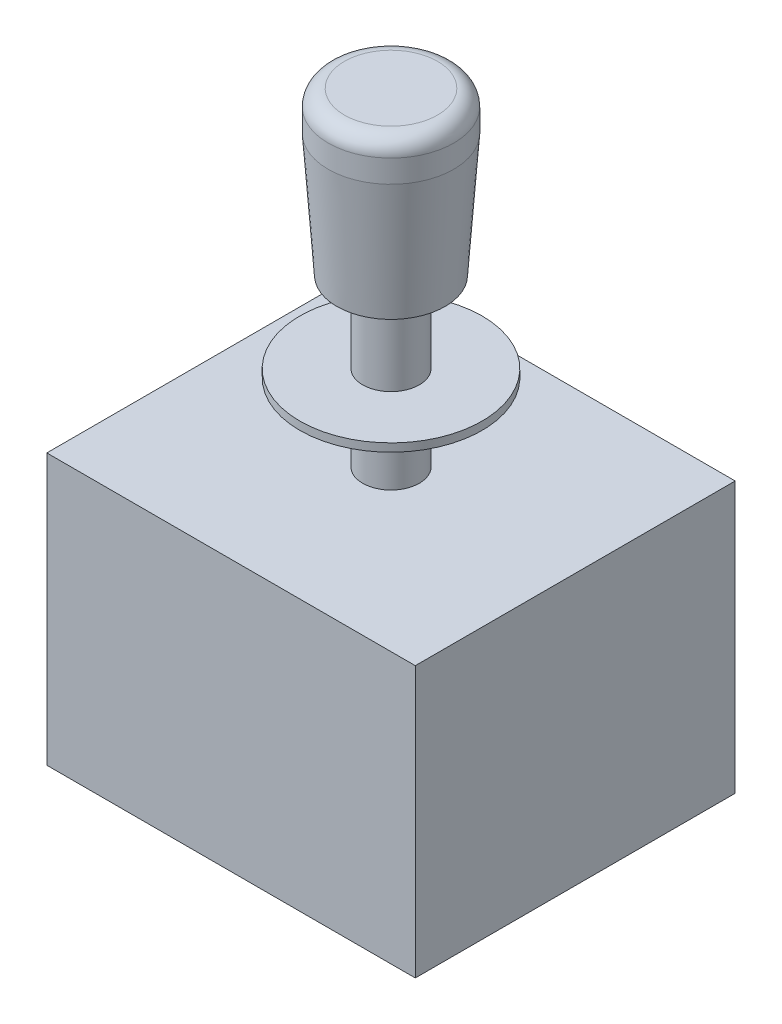
SolidWorks part; units mm, degrees
ref_plane "Front Plane" through (0, 0, 0) normal (0, 0, 1) x (1, 0, 0)
ref_plane "Top Plane" through (0, 0, 0) normal (0, 1, 0) x (1, 0, 0)
ref_plane "Right Plane" through (0, 0, 0) normal (1, 0, 0) x (0, 0, -1)
sketch "Sketch1" plane through (0, 0, 0) normal (0, 0, 1) x (1, 0, 0)
  line L0 (0, 0) -> (-7, 0)
  line L1 (-7, 0) -> (-7, 41)
  line L2 (-7, 41) -> (-13.3697, 41)
  line L3 (-13.3697, 41) -> (-15.5, 71.4018)
  line L4 (-15.5, 71.4018) -> (-15.5, 77)
  line L5 (-11.5, 81) -> (0, 81)
  line L6 (0, 81) -> (0, 0)
  line L7 (0, 0) -> (0, -10.9846) construction
  arc A0 (-15.5, 77) -> (-11.5, 81) centre (-11.5, 77) cw
  dimension "D4" = 4
  dimension "D1" = 14
  dimension "D2" = 81
  dimension "D3" = 31
  dimension "D5" = 40
revolve "Revolve1" add sketch "Sketch1" angle 360 about L7
sketch "Sketch2" plane through (0, 0, 0) normal (0, 0, 1) x (1, 0, 0)
  line L0 (-7, 41) -> (-7, 0) construction
  line L1 (-7, 21.05) -> (-22.5, 21.05)
  line L2 (-7, 21.05) -> (-7, 19.05)
  line L3 (-7, 19.05) -> (-22.5, 19.05)
  line L4 (-22.5, 21.05) -> (-22.5, 19.05)
  line L5 (0, 0) -> (0, 28.9151) construction
  line L6 (-7, 0) -> (7, 0) construction
  dimension "D1" = 2
  dimension "D2" = 45
  dimension "D3" = 19.05
revolve "Revolve2" add sketch "Sketch2" angle 360 about L5
sketch "Sketch3" plane through (0, 0, 0) normal (0, -1, 0) x (1, 0, 0)
  line L1 (45.5, 39.5) -> (-45.5, 39.5)
  line L2 (45.5, 39.5) -> (45.5, -39.5)
  line L3 (45.5, -39.5) -> (-45.5, -39.5)
  line L4 (-45.5, 39.5) -> (-45.5, -39.5)
  line L5 (45.5, 39.5) -> (-45.5, -39.5) construction
  line L6 (45.5, -39.5) -> (-45.5, 39.5) construction
  point P0 (0, 0)
  dimension "D1" = 79
  dimension "D2" = 91
extrude "Boss-Extrude1" add sketch "Sketch3" along normal blind 66.8
